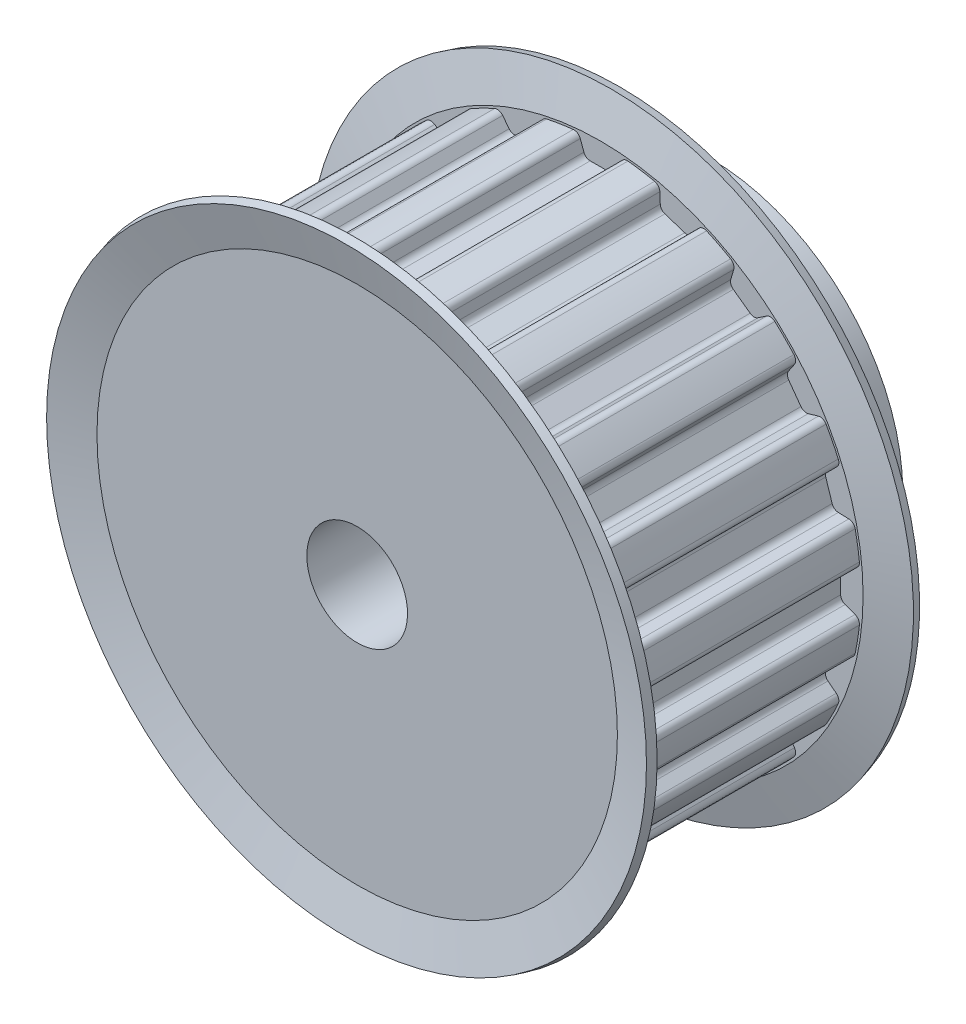
SolidWorks part; units mm, degrees
material "Д16Т ГОСТ 4784-74"
ref_plane "Front" through (0, 0, 0) normal (0, 0, 1) x (1, 0, 0)
ref_plane "Top" through (0, 0, 0) normal (0, 1, 0) x (1, 0, 0)
ref_plane "Right" through (0, 0, 0) normal (1, 0, 0) x (0, 0, -1)
sketch "support-front-body" plane through (0, 0, 0) normal (0, 0, 1) x (1, 0, 0)
  line L0 (0, 0) -> (0, 15.5) construction
  line L1 (0, 0) -> (0, -15.5) construction
  line L2 (0, 0) -> (15.5, 0) construction
  line L3 (0, 0) -> (-15.5, 0) construction
  circle A0 centre (0, 0) radius 15.5
  dimension "diam-outer" = 31
sketch "support-right-body" plane through (0, 0, 0) normal (1, 0, 0) x (0, 0, -1)
  line L0 (0, 0) -> (15, 0) construction
  line L1 (0, 15.5) -> (15, 15.5)
  line L2 (0, 15.5) -> (0, -15.5)
  line L3 (0, -15.5) -> (15, -15.5)
  line L4 (15, 15.5) -> (15, -15.5)
  dimension "width" = 15
sketch "support-right-hub" plane through (0, 0, 0) normal (1, 0, 0) x (0, 0, -1)
  line L0 (21, 0) -> (15, 0) construction
  line L1 (15, 11.5) -> (21, 11.5)
  line L2 (15, 11.5) -> (15, -11.5)
  line L3 (15, -11.5) -> (21, -11.5)
  line L4 (21, 11.5) -> (21, -11.5)
  line L5 (15, 15.5) -> (15, -15.5) construction
  line L6 (0, 0) -> (15, 0) construction
  line L8 (0, 15.5) -> (0, -15.5) construction
  dimension "diam-hub" = 23
  dimension "dist-hub" = 21
sketch "support-right-bore" plane through (0, 0, 0) normal (1, 0, 0) x (0, 0, -1)
  line L0 (0, 15.5) -> (0, -15.5) construction
  line L1 (0, 3) -> (21, 3)
  line L2 (0, 3) -> (0, -3)
  line L3 (0, -3) -> (21, -3)
  line L4 (21, 11.5) -> (21, -11.5) construction
  line L5 (21, 0) -> (0, 0) construction
  line L6 (0, 0) -> (15, 0) construction
  line L7 (21, 3) -> (21, -3)
  line L8 (21, -3) -> (21, 3) construction
  dimension "diam-bore" = 6
sketch "support-stop-screw-hole" plane through (0, 0, 0) normal (1, 0, 0) x (0, 0, -1)
  line L1 (6.5667, 11) -> (9.4333, 11)
  line L2 (6.5667, 11) -> (6.5667, -1)
  line L3 (8, -1) -> (9.4333, -1)
  line L4 (9.4333, 11) -> (9.4333, -1)
  line L5 (8, -1) -> (8, 11) construction
  line L6 (8, -1) -> (6.5667, -1)
  line L7 (0, 0) -> (8, 0) construction
  line L8 (0, 15.5) -> (0, -15.5) construction
  dimension "diam-stop-screw-hole" = 2.8665
  dimension "dist-stop-screw-hole" = 8
  dimension "depth-stop-screw-hole" = 12
  dimension "angle-stop-screw-hole" = 180
  dimension "height-stop-screw-hole" = 11
sketch "support-front-keygroove" plane through (0, 0, 0) normal (0, 0, 1) x (1, 0, 0)
  line L0 (0, 0) -> (0, -3) construction
  line L1 (-1, 5) -> (1, 5)
  line L2 (-1, 5) -> (-1, 2.8)
  line L3 (-1, 2.8) -> (1, 2.8)
  line L4 (1, 5) -> (1, 2.8)
  line L5 (0, 0) -> (0, 3) construction
  circle A0 centre (0, 0) radius 3 construction
  dimension "width-keygroove" = 2
  dimension "dist-keygroove" = 8
  dimension "height-keygroove" = 2.2
sketch "support-front-tooth" plane through (0, 0, 0) normal (0, 0, 1) x (1, 0, 0)
  line L0 (0, 0) -> (0, 16.6142) construction
  line L1 (-1.2106, 15.1532) -> (-0.9958, 14.5632)
  line L2 (-1.6285, 16.6142) -> (1.6285, 16.6142)
  line L3 (1.6285, 16.6142) -> (1.6285, 15.4142)
  line L4 (-1.6285, 16.6142) -> (-1.6285, 15.4142)
  line L5 (-2.5, 16.6142) -> (2.5, 16.6142) construction
  line L6 (1.6285, 15.4142) -> (2.5, 16.6142) construction
  line L7 (0, 15.5) -> (0, 14.3) construction
  line L8 (0, 15.5) -> (1.6285, 15.5) construction
  line L10 (-0.6199, 14.3) -> (0.6199, 14.3)
  line L11 (1.2106, 15.1532) -> (0.9958, 14.5632)
  line L12 (-0.9958, 14.5632) -> (-0.9, 14.3) construction
  line L13 (-0.9, 14.3) -> (-0.6199, 14.3) construction
  line L14 (0.9958, 14.5632) -> (0.9, 14.3) construction
  line L15 (0.9, 14.3) -> (0.6199, 14.3) construction
  circle A0 centre (0, 0) radius 15.5 construction
  arc A1 (-0.9958, 14.5632) -> (-0.6199, 14.3) centre (-0.6199, 14.7) ccw
  arc A3 (1.6285, 15.4142) -> (1.2106, 15.1532) centre (1.5864, 15.0164) ccw
  circle A4 centre (0, 0) radius 15.5 construction
  arc A5 (-1.6285, 15.4142) -> (-1.2106, 15.1532) centre (-1.5864, 15.0164) cw
  arc A6 (0.9958, 14.5632) -> (0.6199, 14.3) centre (0.6199, 14.7) cw
  point P26 (0, 14.3)
  dimension "rad-top" = 0.4
  dimension "rad-bottom" = 0.4
  dimension "height-tooth" = 1.2
  dimension "pitch" = 5
  dimension "angle" = 40
  dimension "width-tooth-bottom" = 1.8
sketch "support-right-flange" plane through (0, 0, 0) normal (1, 0, 0) x (0, 0, -1)
  line L0 (0, 13.585) -> (0, 15.5)
  line L1 (15, 15.5) -> (15, -15.5) construction
  line L2 (0, 15.5) -> (0.5, 15.5) construction
  line L3 (0.5, 15.634) -> (-0.134, 18)
  line L4 (-0.634, 17.866) -> (-0.134, 18)
  line L5 (0.5, 15.634) -> (0.5, 13.585)
  line L6 (0.5, 13.585) -> (0, 13.585)
  line L7 (7.5, 15.5) -> (7.5, 0) construction
  line L8 (0, 15.5) -> (15, 15.5) construction
  line L9 (0, 15.5) -> (-0.634, 17.866)
  line L10 (14.5, 13.585) -> (15, 13.585)
  line L11 (14.5, 15.634) -> (14.5, 13.585)
  line L12 (15.634, 17.866) -> (15.134, 18)
  line L13 (14.5, 15.634) -> (15.134, 18)
  line L14 (15, 15.5) -> (15.634, 17.866)
  line L15 (15, 13.585) -> (15, 15.5)
  line L16 (15, 0) -> (0, 0) construction
  line L17 (15, -13.585) -> (15, -15.5)
  line L18 (15, -15.5) -> (15.634, -17.866)
  line L19 (14.5, -15.634) -> (15.134, -18)
  line L20 (15.634, -17.866) -> (15.134, -18)
  line L21 (14.5, -15.634) -> (14.5, -13.585)
  line L22 (14.5, -13.585) -> (15, -13.585)
  line L23 (0.5, -13.585) -> (0, -13.585)
  line L24 (0.5, -15.634) -> (0.5, -13.585)
  line L25 (-0.634, -17.866) -> (-0.134, -18)
  line L26 (0.5, -15.634) -> (-0.134, -18)
  line L27 (0, -15.5) -> (-0.634, -17.866)
  line L28 (0, -13.585) -> (0, -15.5)
  line L29 (0, 0) -> (15, 0) construction
  line L30 (0, 15.5) -> (0.5, 15.634) construction
  line L31 (0.25, 13.585) -> (0.25, 14.5425) construction
  line L32 (0.25, 14.5425) -> (0.25, 15.5) construction
  line L33 (-0.384, 17.933) -> (0.25, 15.567) construction
  line L34 (0, 15.5) -> (15, 15.5) construction
  line L35 (0, 15.5) -> (0, -15.5) construction
  dimension "angle-flange" = 15
  dimension "thickness-flange" = 0.5
  dimension "diam-flange-inner" = 27.17
  dimension "diam-flange-outer" = 36
  dimension "diam-flange-angle" = 31
ref_axis "ref-axis-center" through (0, 0, -15) along (0, 0, 1)
ref_plane "ref-plane-front" through (0, 0, 0) normal (0, 0, 1) x (1, 0, 0)
ref_plane "ref-plane-back" through (0, 0, -15) normal (0, 0, 1) x (1, 0, 0)
ref_plane "ref-plane-hub-front" through (0, 0, -15) normal (0, 0, 1) x (1, 0, 0)
ref_plane "ref-plane-hub-back" through (0, 0, -21) normal (0, 0, 1) x (1, 0, 0)
ref_plane "ref-plane-bore-front" through (0, 0, 0) normal (0, 0, 1) x (1, 0, 0)
ref_plane "ref-plane-bore-back" through (0, 0, -21) normal (0, 0, 1) x (1, 0, 0)
ref_plane "ref-plane-stop-screw-hole-top" through (0, 11, 0) normal (0, 1, 0) x (-1, 0, 0)
ref_axis "ref-axis-stop-screw-hole" through (0, 11, -8) along (0, -1, 0)
sketch "Sketch5" plane through (0, 0, 0) normal (1, 0, 0) x (0, 0, -1)
  line L0 (15, 15.5) -> (15, -15.5) construction
  line L1 (0, 15.5) -> (15, 15.5) construction
  line L2 (0, 15.5) -> (0, -15.5) construction
  line L3 (0, 0) -> (15, 0) construction
  line L4 (15, 15.5) -> (15, 0)
  line L5 (0, 15.5) -> (15, 15.5)
  line L6 (0, 15.5) -> (0, 0)
  line L7 (0, 0) -> (15, 0) construction
  line L8 (0, 0) -> (15, 0)
revolve "body" add sketch "Sketch5" angle 360 about L7
sketch "Sketch16" plane through (0, 0, 0) normal (1, 0, 0) x (0, 0, -1)
  line L0 (21, 11.5) -> (21, -11.5) construction
  line L1 (15, 11.5) -> (21, 11.5) construction
  line L2 (21, 0) -> (15, 0) construction
  line L3 (15, 11.5) -> (15, -11.5) construction
  line L4 (21, 11.5) -> (21, 0)
  line L5 (15, 11.5) -> (21, 11.5)
  line L6 (21, 0) -> (15, 0) construction
  line L7 (15, 11.5) -> (15, 0)
  line L8 (21, 0) -> (15, 0)
revolve "body-hub" add sketch "Sketch16" angle 360 about L6
sketch "Sketch17" plane through (0, 0, 0) normal (1, 0, 0) x (0, 0, -1)
  line L1 (21, 0) -> (0, 0) construction
  line L2 (0, 3) -> (21, 3) construction
  line L3 (0, 3) -> (0, -3) construction
  line L4 (21, 3) -> (21, -3) construction
  line L5 (21, 0) -> (0, 0) construction
  line L6 (0, 3) -> (21, 3)
  line L7 (0, 3) -> (0, 0)
  line L8 (21, 0) -> (0, 0)
  line L9 (21, 3) -> (21, 0)
revolve "body-bore" cut sketch "Sketch17" angle 360 about L5
sketch "Sketch19" plane through (0, 0, 0) normal (1, 0, 0) x (0, 0, -1)
  line L0 (6.5667, 11) -> (9.4333, 11) construction
  line L1 (8, -1) -> (8, 11) construction
  line L2 (9.4333, 11) -> (9.4333, -1) construction
  line L3 (8, -1) -> (9.4333, -1) construction
  line L4 (8, 11) -> (9.4333, 11)
  line L5 (8, -1) -> (8, 11) construction
  line L6 (9.4333, 11) -> (9.4333, -1)
  line L7 (8, -1) -> (9.4333, -1)
  line L8 (8, -1) -> (8, 11)
revolve "body-stop-screw-hole" [suppressed] cut sketch "Sketch19" angle 360 about L5
pattern_circular "pattern-stop-screw-hole" [suppressed] count 2 every 90 about axis through (0, 0, -15) along (0, 0, 1)
sketch "Sketch21" plane through (0, 0, 0) normal (0, 0, 1) x (1, 0, 0)
  line L0 (-1, 5) -> (1, 5) construction
  line L1 (-1, 5) -> (-1, 2.8) construction
  line L2 (-1, 2.8) -> (1, 2.8) construction
  line L3 (1, 5) -> (1, 2.8) construction
  line L4 (-1, 5) -> (1, 5)
  line L5 (-1, 5) -> (-1, 2.8)
  line L6 (-1, 2.8) -> (1, 2.8)
  line L7 (1, 5) -> (1, 2.8)
extrude "cut-keygroove" [suppressed] cut sketch "Sketch21" against normal up to surface (17.5 mm away)
sketch "Sketch23" plane through (0, 0, 0) normal (0, 0, 1) x (1, 0, 0)
  line L6 (1.6285, 16.6142) -> (-1.6285, 16.6142)
  line L7 (1.6285, 15.4142) -> (1.6285, 16.6142)
  line L8 (0.9958, 14.5632) -> (1.2106, 15.1532)
  line L9 (-0.6199, 14.3) -> (0.6199, 14.3)
  line L10 (-1.2106, 15.1532) -> (-0.9958, 14.5632)
  line L11 (-1.6285, 16.6142) -> (-1.6285, 15.4142)
  line L12 (1.6285, 16.6142) -> (-1.6285, 16.6142)
  line L13 (1.6285, 15.4142) -> (1.6285, 16.6142)
  line L14 (0.9958, 14.5632) -> (1.2106, 15.1532)
  line L15 (-0.6199, 14.3) -> (0.6199, 14.3)
  line L16 (-1.2106, 15.1532) -> (-0.9958, 14.5632)
  line L17 (-1.6285, 16.6142) -> (-1.6285, 15.4142)
  arc A4 (1.6285, 15.4142) -> (1.2106, 15.1532) centre (1.5864, 15.0164) ccw
  arc A5 (0.6199, 14.3) -> (0.9958, 14.5632) centre (0.6199, 14.7) ccw
  arc A6 (-0.9958, 14.5632) -> (-0.6199, 14.3) centre (-0.6199, 14.7) ccw
  arc A7 (-1.2106, 15.1532) -> (-1.6285, 15.4142) centre (-1.5864, 15.0164) ccw
  arc A8 (1.6285, 15.4142) -> (1.2106, 15.1532) centre (1.5864, 15.0164) ccw
  arc A9 (0.6199, 14.3) -> (0.9958, 14.5632) centre (0.6199, 14.7) ccw
  arc A10 (-0.9958, 14.5632) -> (-0.6199, 14.3) centre (-0.6199, 14.7) ccw
  arc A11 (-1.2106, 15.1532) -> (-1.6285, 15.4142) centre (-1.5864, 15.0164) ccw
  dimension "D1" = 0
extrude "cut-tooth" cut sketch "Sketch23" against normal up to surface (15 mm away) up to plane "ref-plane-back"
pattern_circular "pattern-tooth" count 20 over 360 about axis through (0, 0, -15) along (0, 0, 1) of "cut-tooth"
sketch "Sketch25" plane through (0, 0, 0) normal (1, 0, 0) x (0, 0, -1)
  line L0 (0, 0) -> (15, 0) construction
  line L1 (0.5, 13.585) -> (0, 13.585) construction
  line L2 (0.5, 15.634) -> (0.5, 13.585) construction
  line L4 (-0.634, 17.866) -> (-0.134, 18) construction
  line L5 (0, 15.5) -> (-0.634, 17.866) construction
  line L6 (0, 13.585) -> (0, 15.5) construction
  line L7 (0, 0) -> (15, 0) construction
  line L8 (0.5, 13.585) -> (0, 13.585)
  line L9 (0.5, 15.634) -> (0.5, 13.585)
  line L10 (-0.634, 17.866) -> (-0.134, 18)
  line L11 (0.5, 15.634) -> (-0.134, 18) construction
  line L12 (0, 15.5) -> (-0.634, 17.866)
  line L13 (0, 13.585) -> (0, 15.5)
  line L14 (0.5, 15.634) -> (-0.134, 18)
revolve "body-flange-front" add sketch "Sketch25" angle 360 about L7
sketch "Sketch26" plane through (0, 0, 0) normal (1, 0, 0) x (0, 0, -1)
  line L0 (15, 0) -> (0, 0) construction
  line L1 (14.5, 13.585) -> (15, 13.585) construction
  line L2 (14.5, 15.634) -> (14.5, 13.585) construction
  line L4 (15.634, 17.866) -> (15.134, 18) construction
  line L5 (15, 15.5) -> (15.634, 17.866) construction
  line L6 (15, 13.585) -> (15, 15.5) construction
  line L7 (15, 0) -> (0, 0) construction
  line L8 (14.5, 13.585) -> (15, 13.585)
  line L9 (14.5, 15.634) -> (14.5, 13.585)
  line L10 (15.634, 17.866) -> (15.134, 18)
  line L11 (14.5, 15.634) -> (15.134, 18) construction
  line L12 (15, 15.5) -> (15.634, 17.866)
  line L13 (15, 13.585) -> (15, 15.5)
  line L14 (14.5, 15.634) -> (15.134, 18)
revolve "body-flange-back" add sketch "Sketch26" angle 360 about L7
equation "\"diam-flange-angle@support-right-flange\" = \"diam-outer@support-front-body\""
equation "\"diam-flange-inner@support-right-flange\"=(\"diam-outer@support-front-body\" - 2 * \"height-tooth@support-front-tooth\" )  * 0.95"
